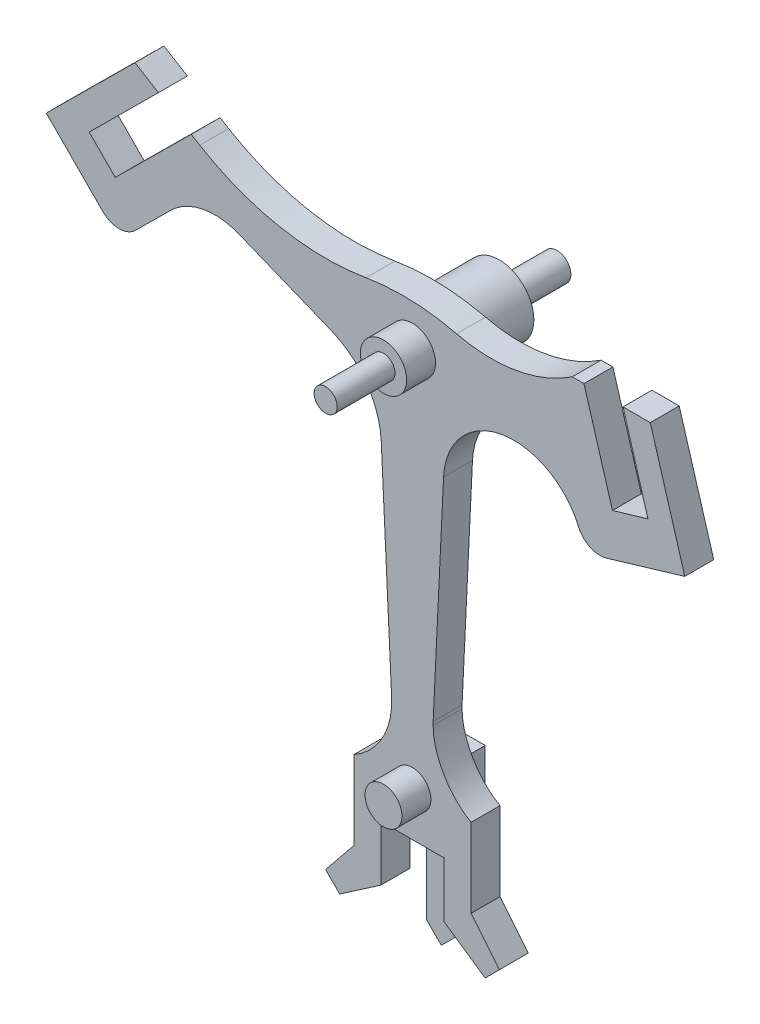
SolidWorks part; units mm, degrees
ref_plane "Alzado" through (0, 0, 0) normal (0, 0, 1) x (1, 0, 0)
ref_plane "Planta" through (0, 0, 0) normal (0, 1, 0) x (1, 0, 0)
ref_plane "Vista lateral" through (0, 0, 0) normal (1, 0, 0) x (0, 0, -1)
ref_plane "Plane1" through (0, 0, -0.125) normal (0, 0, -1) x (-1, 0, 0)
sketch "Sketch1" plane through (0, 0, -0.125) normal (0, 0, -1) x (-1, 0, 0)
  line L0 (-0.2724, -3.6671) -> (0.2724, -3.6671)
  line L1 (0.2724, -3.6671) -> (0.2724, -4.1439)
  line L2 (0.2724, -4.1439) -> (0.8731, -4.1439)
  line L3 (0.8731, -4.1439) -> (1.0516, -3.9651)
  line L4 (1.0516, -3.9651) -> (0.5067, -3.9651)
  line L5 (0.5067, -3.9651) -> (0.5067, -3.2837)
  line L6 (0.1794, -2.6924) -> (0.2908, -0.3715)
  line L7 (0.2908, -0.3715) -> (1.8352, 0.2527)
  line L8 (1.8352, 0.2527) -> (2.5369, -0.4433)
  line L9 (2.5369, -0.4433) -> (3.1657, 0.1906)
  line L10 (3.1657, 0.1906) -> (2.399, 0.9512)
  line L11 (2.399, 0.9512) -> (1.8384, 0.6134)
  line L12 (-1.1689, 1.5441) -> (-1.7297, -0.3375)
  line L13 (-1.7297, -0.3375) -> (-1.821, -0.3106)
  line L14 (-1.821, -0.3106) -> (-1.821, 0.484)
  line L15 (-1.821, 0.484) -> (-2.0567, 0.484)
  line L16 (-2.0567, 0.484) -> (-2.0567, -0.6074)
  line L17 (-2.0567, -0.6074) -> (-1.4827, -0.7784)
  line L18 (-0.2694, -0.8173) -> (-0.1794, -2.6924)
  line L19 (-0.5074, -3.2837) -> (-0.5074, -3.9651)
  line L20 (-0.5074, -3.9651) -> (-1.0516, -3.9651)
  line L21 (-1.0516, -3.9651) -> (-0.6288, -4.3887)
  line L22 (-0.6288, -4.3887) -> (-0.2724, -4.1439)
  line L23 (-0.2724, -4.1439) -> (-0.2724, -3.6671)
  arc A0 (0.5067, -3.2837) -> (0.1794, -2.6924) centre (0.8216, -2.7232) cw
  arc A1 (1.8384, 0.6134) -> (-1.1689, 1.5441) centre (0.7498, 2.42) cw
  arc A2 (-1.4827, -0.7784) -> (-0.2694, -0.8173) centre (-0.8776, -0.8465) cw
  spline S0 degree 3 poles (-0.1794, -2.7232) (-0.1792, -2.7129) (-0.1792, -2.7026) (-0.1794, -2.6924) knots 0 0 0 0 1 1 1 1
  spline S1 degree 3 poles (-0.5074, -3.2837) (-0.3199, -3.1784) (-0.1794, -2.9411) (-0.1794, -2.7232) knots 0 0 0 0 1 1 1 1
  dimension "D1" = 0.6429
  dimension "D2" = 2.1092
  dimension "D3" = 0.6089
  dimension "D4" = 0.2356
  dimension "D5" = 0.327
  dimension "D6" = 0.574
  dimension "D7" = 0.8877
  dimension "D8" = 1.0051
  dimension "D9" = 1.1791
  dimension "D10" = 1.4279
  dimension "D11" = 1.5492
  dimension "D12" = 1.7842
  dimension "D13" = 1.7873
  dimension "D14" = 1.8772
  dimension "D15" = 1.8772
  dimension "D16" = 2.2361
  dimension "D17" = 2.3291
  dimension "D18" = 2.3474
  dimension "D19" = 2.5634
  dimension "D20" = 2.8065
  dimension "D21" = 2.8783
  dimension "D22" = 2.9298
  dimension "D23" = 3.1082
  dimension "D24" = 3.8918
  dimension "D25" = 3.8951
  dimension "D26" = 4.4556
  dimension "D27" = 4.5935
  dimension "D28" = 5.2223
  dimension "D29" = 0.1788
  dimension "D30" = 0.4768
  dimension "D31" = 0.8602
  dimension "D32" = 3.5365
  dimension "D33" = 4.7573
  dimension "D38" = 3.7006
  dimension "D40" = 3.8064
  dimension "D41" = 3.8333
  dimension "D42" = 4.3345
  dimension "D43" = 4.3966
  dimension "D44" = 4.6279
  dimension "D49" = 0.2448
extrude "Boss-Extrude1" add sketch "Sketch1" against normal blind 0.25
sketch "Sketch2" plane through (0, 0, -0.125) normal (0, 0, -1) x (-1, 0, 0)
  line L0 (-0.1297, -3.1468) -> (0.1297, -3.1468)
  line L1 (0.1297, -3.1468) -> (0.1297, -4.454)
  line L2 (0.1297, -4.454) -> (0, -4.5837)
  line L3 (0, -4.5837) -> (-0.1297, -4.454)
  line L4 (-0.1297, -4.454) -> (-0.1297, -3.1468)
  line L5 (-0.2724, -4.1439) -> (-0.2724, -3.6671) construction
  line L6 (0.2724, -4.1439) -> (0.8731, -4.1439) construction
  dimension "D1" = 0.1427
  dimension "D2" = 0.2724
  dimension "D3" = 0.4021
  dimension "D4" = 0.9971
  dimension "D5" = 0.3101
  dimension "D6" = 0.4398
extrude "Boss-Extrude2" add sketch "Sketch2" along normal blind 0.25
sketch "Sketch3" plane through (0, 0, 0.125) normal (0, 0, 1) x (1, 0, 0)
  line L0 (-2.1954, 0.8285) -> (-2.7944, 0.2343)
  line L1 (-2.7944, 0.2343) -> (-2.5691, 0.0071)
  line L2 (-2.5691, 0.0071) -> (-1.9127, 0.6581)
  line L3 (-1.9127, 0.6581) -> (-2.1954, 0.8285)
  line L4 (2.0567, 0.484) -> (2.0567, -0.6074) construction
  line L5 (1.821, 0.484) -> (2.0567, 0.484) construction
  dimension "D1" = 3.9694
  dimension "D2" = 4.252
  dimension "D3" = 4.6257
  dimension "D4" = 4.8511
  dimension "D5" = 0.1741
  dimension "D6" = 0.3444
  dimension "D7" = 0.2498
  dimension "D8" = 0.4769
extrude "Cut-Extrude1" cut sketch "Sketch3" against normal through all
sketch "Sketch4" plane through (0, 0, 0.125) normal (0, 0, 1) x (1, 0, 0)
  line L0 (1.4651, 0.5502) -> (1.1689, 1.5441)
  line L1 (0.2724, -4.1439) -> (0.2724, -3.6671) construction
  line L2 (-0.2724, -4.1439) -> (-0.8731, -4.1439) construction
  arc A0 (-0.4006, 0.3399) -> (0.3822, 0.3116) centre (-0.0782, -1.5803) cw
  arc A1 (0.3822, 0.3116) -> (1.4651, 0.5502) centre (0.6801, 1.5359) ccw
  arc A2 (1.1689, 1.5441) -> (-0.4006, 0.3399) centre (-0.7498, 2.42) cw
  dimension "D1" = 1.9471
  dimension "D2" = 1.2601
  dimension "D3" = 2.1092
  dimension "D4" = 0.1098
  dimension "D5" = 0.4077
  dimension "D6" = 0.8965
  dimension "D7" = 1.1927
  dimension "D8" = 0.673
  dimension "D9" = 2.5636
extrude "Cut-Extrude2" cut sketch "Sketch4" against normal through all
draft "Draft1" type of draft neutral plane draft angle 34.486 faces to draft 1 face at (-0.5728, -4.1439, 0) neutral plane through (-0.2724, -3.6671, 0.125) neutral plane normal (1, 0, 0) parameters "D1"=34.486
draft "Draft2" type of draft neutral plane draft angle 50.981 faces to draft 1 face at (-0.7791, -3.9651, 0) neutral plane through (-0.5067, -3.9651, 0.125) neutral plane normal (-1, 0, 0) parameters "D1"=50.981
draft "Draft3" type of draft neutral plane draft angle 16.595 faces to draft 1 face at (2.0567, -0.0617, 0) neutral plane through (1.821, 0.484, 0.125) neutral plane normal (0, 1, 0) parameters "D1"=16.595
draft "Draft4" type of draft neutral plane draft angle 16.433 faces to draft 1 face at (1.821, 0.0867, 0) neutral plane through (1.821, 0.484, 0.125) neutral plane normal (0, 1, 0) reverse direction yes parameters "D1"=16.433
draft "Draft5" type of draft neutral plane draft angle 50.981 faces to draft 1 face at (0.7795, -3.9651, 0) neutral plane through (0.5074, -3.2837, 0.125) neutral plane normal (1, 0, 0) parameters "D1"=50.981
ref_plane "Plane2" through (0, -3.2865, 0) normal (0, -1, 0) x (1, 0, 0)
sketch "Sketch5" plane through (0, -3.2865, 0) normal (0, -1, 0) x (1, 0, 0)
  line L0 (0.16, 0.375) -> (0, 0.375)
  line L1 (0, 0.375) -> (0, 0.125)
  line L2 (0, 0.125) -> (0.16, 0.125)
  line L3 (0.16, 0.125) -> (0.16, 0.375)
  line L4 (0, 0.375) -> (0, 0.125) construction
  dimension "D1" = 0.16
  dimension "D2" = 0.25
revolve "Revolve1" add sketch "Sketch5" angle 360 about L4 reverse direction yes
ref_plane "Plane3" through (0, 0, 0) normal (0, -1, 0) x (1, 0, 0)
sketch "Sketch6" plane through (0, 0, 0) normal (0, -1, 0) x (1, 0, 0)
  line L0 (0.1, 0.875) -> (0, 0.875)
  line L1 (0, 0.875) -> (0, 0.125)
  line L2 (0, 0.125) -> (0.2, 0.125)
  line L3 (0.2, 0.125) -> (0.2, 0.375)
  line L4 (0.2, 0.375) -> (0.1, 0.375)
  line L5 (0.1, 0.375) -> (0.1, 0.875)
  line L6 (0, 0.875) -> (0, 0.125) construction
  dimension "D1" = 0.1
  dimension "D2" = 0.2
  dimension "D3" = 0.25
  dimension "D4" = 0.75
revolve "Revolve2" add sketch "Sketch6" angle 360 about L6 reverse direction yes
sketch "Sketch7" plane through (0, 0, 0) normal (0, 1, 0) x (1, 0, 0)
  line L0 (0.12, 1.125) -> (0, 1.125)
  line L1 (0, 1.125) -> (0, 0.125)
  line L2 (0, 0.125) -> (0.3, 0.125)
  line L3 (0.3, 0.125) -> (0.3, 0.625)
  line L4 (0.3, 0.625) -> (0.12, 0.625)
  line L5 (0.12, 0.625) -> (0.12, 1.125)
  line L6 (0, 1.125) -> (0, 0.125) construction
  dimension "D1" = 0.12
  dimension "D2" = 0.3
  dimension "D3" = 0.5
  dimension "D4" = 1
revolve "Revolve3" add sketch "Sketch7" angle 360 about L6 reverse direction yes
chamfer "Chamfer1" distance 0.0638 angle 73.405 1 edges at (1.4651, 0.5502, 0) first distance on face at (1.5974, 0.1064, 0)
fillet "Fillet1" radius 0.2 2 edges at (1.4827, -0.7784, 0) (-2.5369, -0.4433, 0) tangent propagation no
fillet "Fillet2" radius 0.5445 1 edges at (-1.8352, 0.2527, 0) tangent propagation no
fillet "Fillet3" radius 0.6972 1 edges at (-0.2908, -0.3715, 0) tangent propagation no
